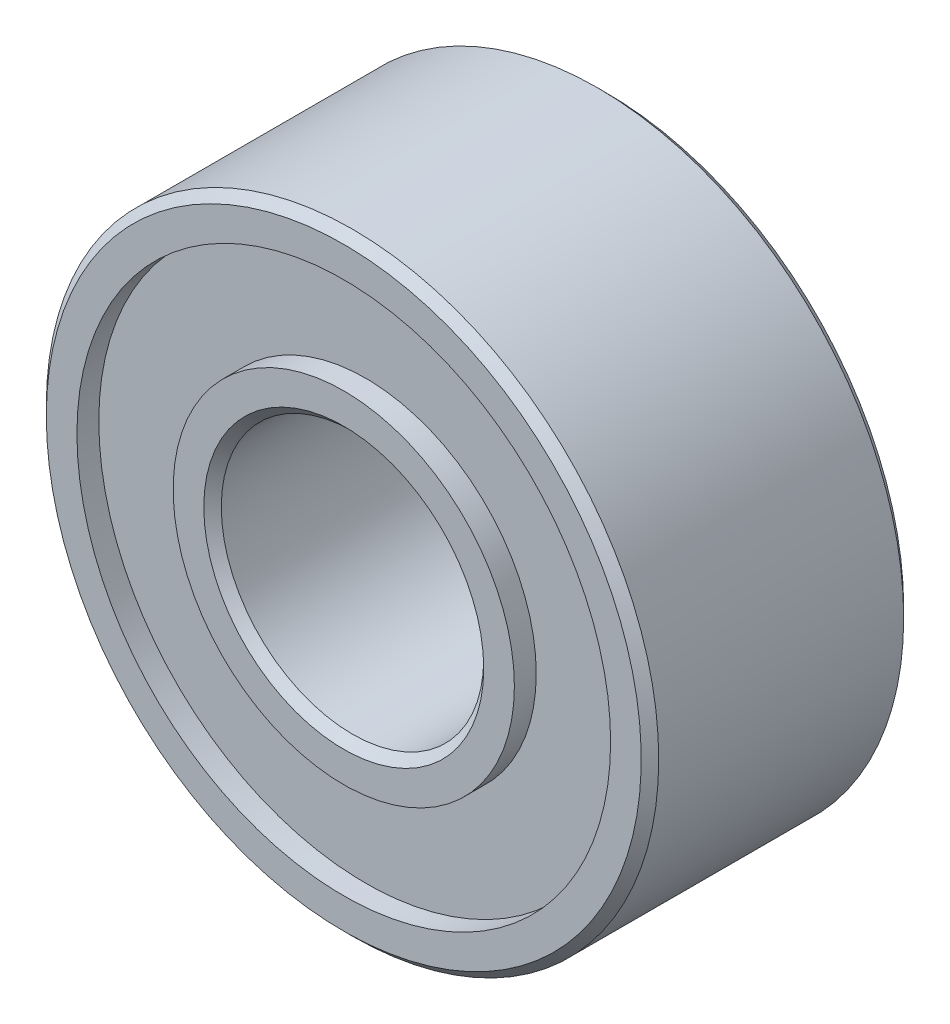
SolidWorks part; units mm, degrees
ref_plane "Ebene vorne" through (0, 0, 0) normal (0, 0, 1) x (1, 0, 0)
ref_plane "Ebene oben" through (0, 0, 0) normal (0, 1, 0) x (1, 0, 0)
ref_plane "Ebene rechts" through (0, 0, 0) normal (1, 0, 0) x (0, 0, -1)
sketch "Skizze2" plane through (0, 0, 0) normal (1, 0, 0) x (0, 0, -1)
  line L0 (-11.8458, 0) -> (13.4965, 0) construction
  line L1 (0, 16.288) -> (0, -14.1034) construction
  line L2 (-1.5, 1.5) -> (1.5, 1.5)
  line L3 (1.5, 1.5) -> (1.5, 1.95)
  line L4 (1.5, 1.95) -> (1.25, 1.95)
  line L5 (1.25, 1.95) -> (1.25, 3.05)
  line L6 (1.25, 3.05) -> (1.5, 3.05)
  line L7 (1.5, 3.05) -> (1.5, 3.5)
  line L8 (1.5, 3.5) -> (-1.5, 3.5)
  line L9 (-1.5, 3.05) -> (-1.5, 3.5)
  line L10 (-1.25, 3.05) -> (-1.5, 3.05)
  line L11 (-1.25, 1.95) -> (-1.25, 3.05)
  line L12 (-1.5, 1.95) -> (-1.25, 1.95)
  line L13 (-1.5, 1.5) -> (-1.5, 1.95)
  point P5 (0, 3.5)
  point P19 (0, 1.5)
  dimension "D1" = 3
  dimension "D2" = 7
  dimension "D3" = 3
  dimension "D4" = 3.9
  dimension "D5" = 6.1
  dimension "D6" = 2.5
revolve "Rotation1" add sketch "Skizze2" angle 360 about L0
ref_axis "Achse1" through (0, 0, -14.7636) along (0, 0, 1)
chamfer "Fase1" distance 0.1 angle 45 4 edges at (1.5, 0, -1.5) (1.5, 0, 1.5) (3.5, 0, -1.5) (3.5, 0, 1.5)
